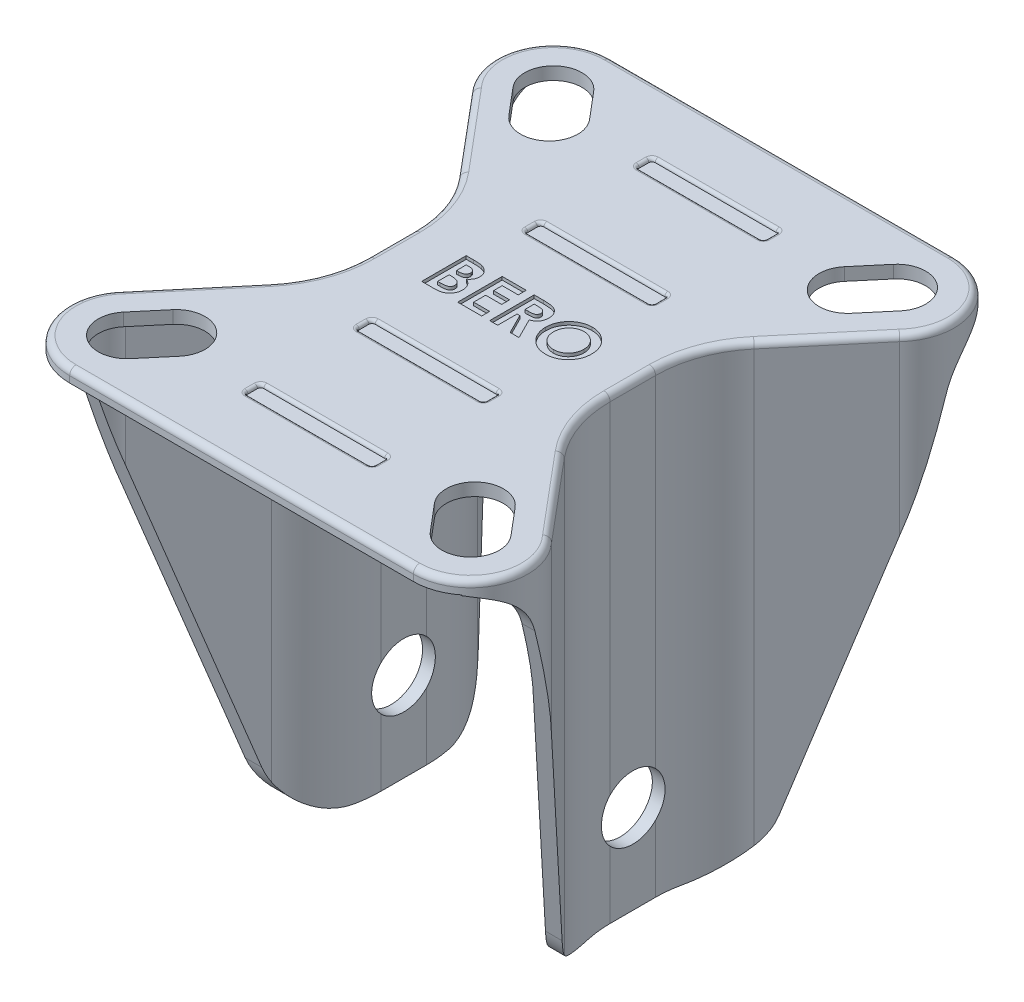
SolidWorks part; units mm, degrees
material "Stainless Steel (ferritic)"
ref_plane "Front Plane" through (0, 0, 0) normal (0, 0, 1) x (1, 0, 0)
ref_plane "Top Plane" through (0, 0, 0) normal (0, 1, 0) x (1, 0, 0)
ref_plane "Right Plane" through (0, 0, 0) normal (1, 0, 0) x (0, 0, -1)
sketch "Sketch1" plane through (0, 0, 0) normal (0, 1, 0) x (1, 0, 0)
  line L1 (9, 85) -> (63, 85)
  line L3 (63, 0) -> (9, 0)
  line L5 (55, 38.9293) -> (55, 46.0707)
  line L6 (17, 46.0707) -> (17, 38.9293)
  line L8 (66.4388, 11.9025) -> (62.894, 16.1024)
  line L9 (56.0163, 10.2974) -> (59.5612, 6.0975)
  line L10 (59.1346, 27.5765) -> (69.5627, 15.1588)
  line L11 (12.8654, 27.5765) -> (2.4373, 15.1588)
  line L12 (12.8654, 57.4235) -> (2.4373, 69.8412)
  line L13 (59.1346, 57.4235) -> (69.5627, 69.8412)
  line L16 (15.9837, 10.2974) -> (12.4388, 6.0975)
  line L17 (5.5612, 11.9025) -> (9.106, 16.1024)
  line L18 (56.0163, 74.7026) -> (59.5612, 78.9025)
  line L19 (66.4388, 73.0975) -> (62.894, 68.8976)
  line L20 (15.9837, 74.7026) -> (12.4388, 78.9025)
  line L21 (5.5612, 73.0975) -> (9.106, 68.8976)
  arc A0 (59.5612, 6.0975) -> (66.4388, 11.9025) centre (63, 9) ccw
  arc A2 (9, 0) -> (2.4373, 15.1588) centre (9, 9) cw
  arc A5 (9, 85) -> (2.4373, 69.8412) centre (9, 76) ccw
  arc A6 (63, 85) -> (69.5627, 69.8412) centre (63, 76) cw
  arc A8 (63, 0) -> (69.5627, 15.1588) centre (63, 9) ccw
  arc A9 (17, 46.0707) -> (12.8654, 57.4235) centre (-0.6534, 46.0707) ccw
  arc A10 (12.8654, 27.5765) -> (17, 38.9293) centre (-0.6534, 38.9293) ccw
  arc A11 (59.1346, 27.5765) -> (55, 38.9293) centre (72.6534, 38.9293) cw
  arc A12 (55, 46.0707) -> (59.1346, 57.4235) centre (72.6534, 46.0707) cw
  arc A14 (62.894, 16.1024) -> (56.0163, 10.2974) centre (59.4552, 13.1999) ccw
  arc A15 (9.106, 16.1024) -> (15.9837, 10.2974) centre (12.5448, 13.1999) cw
  arc A16 (12.4388, 6.0975) -> (5.5612, 11.9025) centre (9, 9) cw
  arc A17 (59.5612, 78.9025) -> (66.4388, 73.0975) centre (63, 76) cw
  arc A18 (62.894, 68.8976) -> (56.0163, 74.7026) centre (59.4552, 71.8001) cw
  arc A19 (12.4388, 78.9025) -> (5.5612, 73.0975) centre (9, 76) ccw
  arc A20 (9.106, 68.8976) -> (15.9837, 74.7026) centre (12.5448, 71.8001) ccw
  dimension "D7" = 9
  dimension "D8" = 67
  dimension "D9" = 58.6002
  dimension "D2" = 17.6534
  dimension "D3" = 54
  dimension "D4" = 9
  dimension "D5" = 5.4959
  dimension "D1" = 85
  dimension "D6" = 7.1415
extrude "Boss-Extrude1" add sketch "Sketch1" along normal blind 2
sketch "Sketch2" plane through (0, 0, 0) normal (0, -1, 0) x (1, 0, 0)
  line L4 (17, -46.0707) -> (17, -38.9293)
  line L6 (55, -38.9293) -> (55, -46.0707)
  line L7 (12.8654, -27.5765) -> (2.4373, -15.1588)
  line L9 (12.8654, -57.4235) -> (2.4373, -69.8412)
  line L11 (69.5627, -69.8412) -> (59.1346, -57.4235)
  line L13 (59.1346, -27.5765) -> (69.5627, -15.1588)
  line L20 (14.397, -26.2904) -> (3.9312, -13.8277)
  line L21 (19, -46.0707) -> (19, -38.9293)
  line L22 (14.397, -58.7096) -> (3.9312, -71.1723)
  line L23 (3.3431, -83) -> (9, -83)
  line L26 (68.0688, -71.1723) -> (57.603, -58.7096)
  line L27 (53, -38.9293) -> (53, -46.0707)
  line L28 (57.603, -26.2904) -> (68.0688, -13.8277)
  line L29 (3.3431, -2) -> (9, -2)
  line L30 (9, -2) -> (63, -2) construction
  line L31 (9, -83) -> (63, -83) construction
  line L32 (9, -85) -> (63, -85) construction
  line L33 (9, 0) -> (63, 0) construction
  line L34 (63, -2) -> (68.6569, -2)
  line L35 (63, -83) -> (68.6569, -83)
  arc A4 (17, -38.9293) -> (12.8654, -27.5765) centre (-0.6534, -38.9293) ccw
  arc A5 (59.1346, -27.5765) -> (55, -38.9293) centre (72.6534, -38.9293) ccw
  arc A6 (55, -46.0707) -> (59.1346, -57.4235) centre (72.6534, -46.0707) ccw
  arc A7 (12.8654, -57.4235) -> (17, -46.0707) centre (-0.6534, -46.0707) ccw
  arc A16 (3.3431, -2) -> (2.4373, -15.1588) centre (9, -9) ccw
  arc A17 (69.5627, -15.1588) -> (68.6569, -2) centre (63, -9) ccw
  arc A18 (68.6569, -83) -> (69.5627, -69.8412) centre (63, -76) ccw
  arc A19 (2.4373, -69.8412) -> (3.3431, -83) centre (9, -76) ccw
  arc A20 (9, -2) -> (3.9312, -13.8277) centre (9, -9) ccw
  arc A21 (19, -38.9293) -> (14.397, -26.2904) centre (-0.6534, -38.9293) ccw
  arc A22 (14.397, -58.7096) -> (19, -46.0707) centre (-0.6534, -46.0707) ccw
  arc A23 (3.9312, -71.1723) -> (9, -83) centre (9, -76) ccw
  arc A28 (63, -83) -> (68.0688, -71.1723) centre (63, -76) ccw
  arc A29 (53, -46.0707) -> (57.603, -58.7096) centre (72.6534, -46.0707) ccw
  arc A30 (57.603, -26.2904) -> (53, -38.9293) centre (72.6534, -38.9293) ccw
  arc A31 (68.0688, -13.8277) -> (63, -2) centre (63, -9) ccw
  arc A32 (2.4373, -69.8412) -> (9, -85) centre (9, -76) ccw construction
  arc A33 (63, -85) -> (69.5627, -69.8412) centre (63, -76) ccw construction
  arc A34 (69.5627, -15.1588) -> (63, 0) centre (63, -9) ccw construction
  arc A35 (9, 0) -> (2.4373, -15.1588) centre (9, -9) ccw construction
  dimension "D1" = 2
extrude "Boss-Extrude3" add sketch "Sketch2" along normal blind 70
sketch "Sketch3" plane through (0, 0, 0) normal (1, 0, 0) x (0, 0, -1)
  line L6 (59.529, -62.6666) -> (74.8383, -7.3334)
  line L7 (-20.9339, -70) -> (35.1089, -70)
  line L9 (25.471, -62.6666) -> (10.1617, -7.3334)
  line L12 (84.4762, 0) -> (105.9339, 0)
  line L13 (105.9339, 0) -> (105.9339, -70)
  line L14 (105.9339, -70) -> (49.8911, -70)
  line L15 (0.5238, 0) -> (-20.9339, 0)
  line L16 (-20.9339, 0) -> (-20.9339, -70)
  arc A0 (84.4762, 0) -> (74.8383, -7.3334) centre (84.4762, -10) ccw
  arc A1 (49.8911, -70) -> (59.529, -62.6666) centre (49.8911, -60) ccw
  arc A2 (35.1089, -70) -> (25.471, -62.6666) centre (35.1089, -60) cw
  arc A3 (0.5238, 0) -> (10.1617, -7.3334) centre (0.5238, -10) cw
  circle A4 centre (42.5, -56) radius 5
  dimension "D2" = 10
  dimension "D1" = 10
fillet "Fillet9" radius 1 5 edges at (62.8359, 0, -20.059) (54.1866, 0, -32.2038) (62.8359, 0, -64.941) (54.1866, 0, -52.7962) (53, 0, -42.5)
fillet "Fillet10" radius 1 5 edges at (9.1641, 0, -64.941) (17.8134, 0, -52.7962) (9.1641, 0, -20.059) (17.8134, 0, -32.2038) (19, 0, -42.5)
extrude "Cut-Extrude2" cut sketch "Sketch3" against normal blind 20 and the other way blind 80
fillet "Fillet11" radius 1 16 edges at (15.9342, 2, -52.1118) (7.6513, 2, -63.6323) (0.7408, 2, -79.5757) (36, 2, -85) (71.2592, 2, -79.5757) (64.3487, 2, -63.6323) (56.0658, 2, -52.1118) (56.0658, 2, -32.8882) (7.6513, 2, -21.3677) (15.9342, 2, -32.8882) (17, 2, -42.5) (64.3487, 2, -21.3677) (55, 2, -42.5) (36, 2, 0) (71.2592, 2, -5.4243) (0.7408, 2, -5.4243)
sketch "Sketch5" plane through (0, 2, 0) normal (0, 1, 0) x (1, 0, 0)
  line L1 (26, 30.5) -> (46, 30.5)
  line L5 (26, 10.5) -> (46, 10.5)
  line L7 (26, 30.5) -> (26, 28)
  line L8 (26, 13) -> (46, 13)
  line L9 (46, 30.5) -> (46, 28)
  line L10 (26, 28) -> (46, 28)
  line L14 (-5.21, 30.5) -> (79.8517, 30.5) construction
  line L15 (-5.21, 28) -> (79.8517, 28) construction
  line L16 (-8.2039, 13) -> (83.7262, 13) construction
  line L17 (-8.2039, 10.5) -> (83.7262, 10.5) construction
  line L18 (46, 13) -> (46, 10.5)
  line L20 (26, 13) -> (26, 10.5)
  line L21 (26, 72) -> (26, 74.5)
  line L23 (46, 72) -> (46, 74.5)
  line L24 (26, 57) -> (46, 57)
  line L25 (46, 54.5) -> (46, 57)
  line L26 (26, 72) -> (46, 72)
  line L27 (26, 54.5) -> (26, 57)
  line L28 (26, 74.5) -> (46, 74.5)
  line L29 (26, 54.5) -> (46, 54.5)
  dimension "D3" = 20
  dimension "D5" = 2.5
  dimension "D4" = 2.5
extrude "Cut-Extrude3" cut sketch "Sketch5" against normal blind 0.5
fillet "Fillet12" radius 0.5 32 edges at (26, 2, -73.25) (36, 2, -72) (36, 2, -74.5) (46, 2, -73.25) (46, 2, -55.75) (36, 2, -57) (26, 2, -55.75) (36, 2, -54.5) (26, 2, -11.75) (36, 2, -13) (36, 2, -10.5) (46, 2, -11.75) (46, 2, -29.25) (26, 2, -29.25) (36, 2, -28) (36, 2, -30.5) (46, 1.75, -13) (46, 1.75, -10.5) (26, 1.75, -10.5) (26, 1.75, -28) (46, 1.75, -30.5) (46, 1.75, -28) (26, 1.75, -54.5) (46, 1.75, -54.5) (46, 1.75, -57) (46, 1.75, -72) (46, 1.75, -74.5) (26, 1.75, -72) (26, 1.75, -74.5) (26, 1.75, -57) (26, 1.75, -30.5) (26, 1.75, -13)
sketch "Sketch7" plane through (0, 2, 0) normal (0, 1, 0) x (1, 0, 0)
  line L3 (24, 39.5) -> (48, 39.5) construction
  text T0 "BERO" font "Century Gothic" height 7
extrude "Cut-Extrude6" cut sketch "Sketch7" against normal blind 0.5
